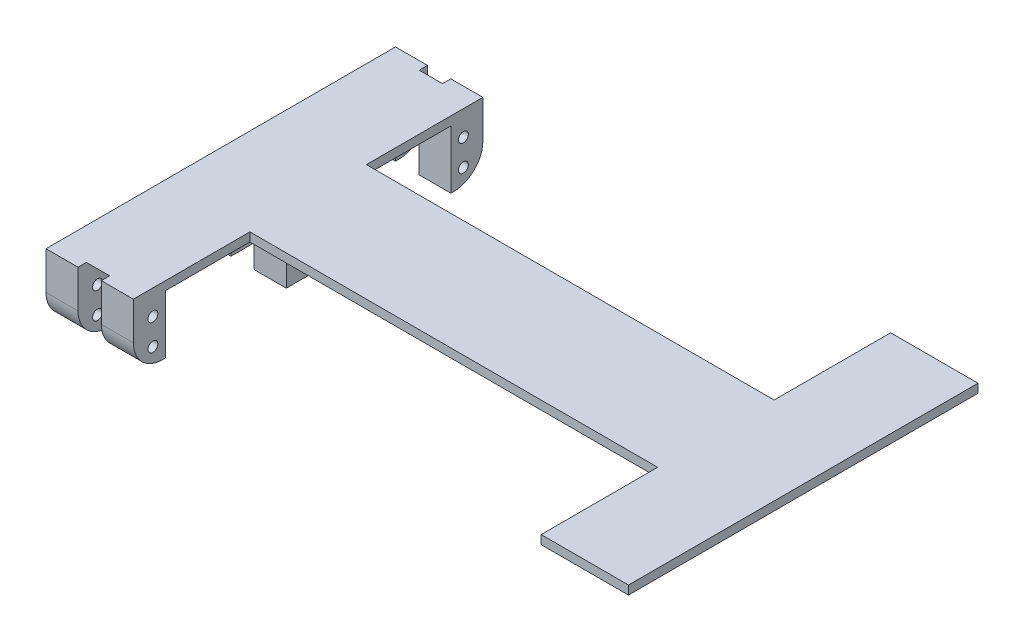
SolidWorks part; units mm, degrees
ref_plane "Front" through (0, 0, 0) normal (0, 0, 1) x (1, 0, 0)
ref_plane "Top" through (0, 0, 0) normal (0, 1, 0) x (1, 0, 0)
ref_plane "Right" through (0, 0, 0) normal (1, 0, 0) x (0, 0, -1)
sketch "스케치1" plane through (0, 0, 0) normal (0, 1, 0) x (1, 0, 0)
  line L0 (100, 0) -> (-100, 0) construction
  line L1 (-100, 60) -> (-70, 60)
  line L2 (-100, 60) -> (-100, -60)
  line L3 (-100, -60) -> (-70, -60)
  line L4 (100, 60) -> (100, -60)
  line L5 (-100, 60) -> (100, -60) construction
  line L6 (-100, -60) -> (100, 60) construction
  line L7 (-70, -20) -> (70, -20)
  line L8 (-70, -20) -> (-70, -60)
  line L10 (70, -20) -> (70, -60)
  line L11 (-70, -20) -> (2.0805, -58.7583) construction
  line L12 (2.0805, -58.7583) -> (70, -20) construction
  line L13 (70, -60) -> (100, -60)
  line L14 (70, 20) -> (70, 60)
  line L15 (-70, 20) -> (-70, 60)
  line L16 (-70, 20) -> (70, 20)
  line L17 (70, 60) -> (100, 60)
  point P0 (0, 0)
  point P6 (2.0805, -58.7583)
  dimension "D1" = 200
  dimension "D2" = 120
  dimension "D3" = 30
  dimension "D4" = 30
  dimension "D5" = 40
extrude "보스-돌출1" add sketch "스케치1" along normal blind 3
sketch "스케치3" plane through (0, 0, 0) normal (0, -1, 0) x (1, 0, 0)
  line L0 (-100, 0) -> (100, 0) construction
  line L1 (-100, -60) -> (-100, 60) construction
  line L2 (100, 60) -> (100, -60) construction
  line L3 (-100, -7.5) -> (-89, -7.5)
  line L4 (-100, 60) -> (-89, 60)
  line L5 (-100, 60) -> (-100, 49)
  line L6 (-100, 49) -> (-89, 49)
  line L7 (-89, 60) -> (-89, 49)
  line L8 (-100, 7.5) -> (-89, 7.5)
  line L9 (-100, 7.5) -> (-100, -7.5)
  line L10 (-100, 0) -> (-89, 0)
  line L11 (-89, 7.5) -> (-89, -7.5)
  line L12 (-100, -60) -> (-100, -49)
  line L13 (-100, -49) -> (-89, -49)
  line L14 (-89, -60) -> (-89, -49)
  line L15 (-100, -60) -> (-89, -60)
  line L18 (-85, 60) -> (-85, -60) construction
  line L19 (-100, 60) -> (-70, 60) construction
  line L20 (-70, -60) -> (-100, -60) construction
  line L21 (-70, -60) -> (-70, -49)
  line L22 (-81, -60) -> (-81, -49)
  line L23 (-70, -60) -> (-81, -60)
  line L24 (-70, -49) -> (-81, -49)
  line L25 (-70, 7.5) -> (-70, -7.5)
  line L26 (-70, -7.5) -> (-81, -7.5)
  line L27 (-81, 7.5) -> (-81, -7.5)
  line L28 (-70, 7.5) -> (-81, 7.5)
  line L29 (-70, 49) -> (-81, 49)
  line L30 (-70, 60) -> (-70, 49)
  line L31 (-70, 60) -> (-81, 60)
  line L32 (-81, 60) -> (-81, 49)
  line M11 (-70, 60) -> (-100, 60)
  line M12 (-100, 60) -> (-100, -60)
  line M13 (-100, -60) -> (-70, -60)
  dimension "D1" = 11
  dimension "D2" = 11
  dimension "D3" = 7.5
  dimension "D4" = 11
extrude "보스-돌출3" add sketch "스케치3" along normal blind 20 contours L11 L10 L9 L3 | L11 L8 L10 M12 | L7 L6 M11 M12 | L14 L13 M13 M12 | L29 L32 L31 L30 | L21 L24 L22 L23 | L25 L26 L27 L28
hole_wizard "M3 여유 구멍1" positions "스케치5" profile "스케치7" hole size "M3" standard "KS"
sketch "스케치5" plane through (-100, 0, 0) normal (-1, 0, 0) x (0, 0, 1)
  line L0 (0, 0) -> (0, -20) construction
  line L1 (7.5, -20) -> (-7.5, -20) construction
  point P0 (-3, -5.5)
  point P6 (-3, -14.5)
  point P12 (-53.3, -5.5)
  point P14 (-53.3, -14.5)
  point P41 (53.3, -5.5)
  point P42 (53.3, -14.5)
  point P43 (3, -14.5)
  point P44 (3, -5.5)
sketch "스케치7" plane through (-100, -5.5, -3) normal (0, 1, 0) x (0, 0, 1)
  line L0 (0, 0) -> (0, 30)
  line L1 (0, 30) -> (1.7, 30)
  line L2 (1.7, 30) -> (1.7, 0)
  line L5 (1.7, 0) -> (0, 0)
  line L11 (0, -6.35) -> (0, 107.95) construction
  dimension "관통 구멍 지름" = 3.4
  dimension "관통 구멍 깊이" = 30
mirror "대칭 복사1" about plane through (0, 0, 0) normal (1, 0, 0) of "M3 여유 구멍1"
fillet "필렛1" radius 10 6 edges at (-85, 0, 60) (-94.5, -20, 60) (-94.5, -20, -60) (-75.5, -20, 60) (-85, 0, -60) (-75.5, -20, -60)
